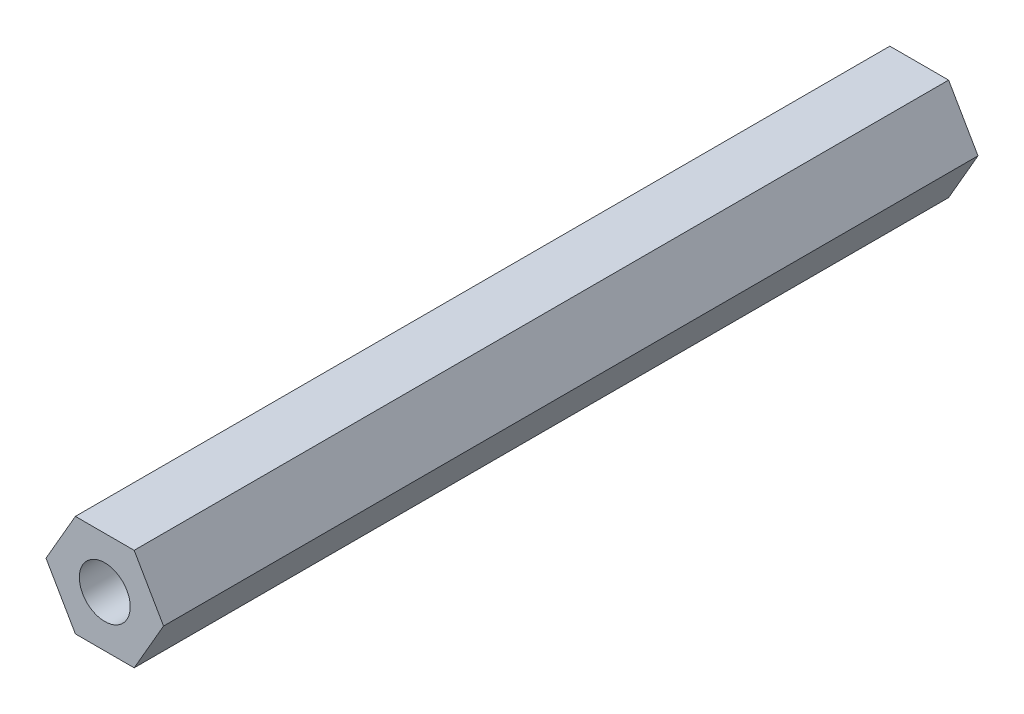
SolidWorks part; units mm, degrees
ref_plane "Front Plane" through (0, 0, 0) normal (0, 0, 1) x (1, 0, 0)
ref_plane "Top Plane" through (0, 0, 0) normal (0, 1, 0) x (1, 0, 0)
ref_plane "Right Plane" through (0, 0, 0) normal (1, 0, 0) x (0, 0, -1)
sketch "Sketch1" plane through (0, 0, 0) normal (0, 0, 1) x (1, 0, 0)
  line L0 (0, 6.35) -> (0, 0)
  line L1 (-7.3323, 0) -> (-3.6662, -6.35)
  line L2 (-3.6662, -6.35) -> (3.6662, -6.35)
  line L3 (3.6662, -6.35) -> (7.3323, 0)
  line L4 (7.3323, 0) -> (3.6662, 6.35)
  line L5 (3.6662, 6.35) -> (-3.6662, 6.35)
  line L6 (-3.6662, 6.35) -> (-7.3323, 0)
  circle A0 centre (0, 0) radius 6.35 construction
  dimension "D1" = 6.35
extrude "Boss-Extrude1" add sketch "Sketch1" along normal offset from surface (514.4834 mm away) 25.4 contours L5 L6 L1 L2 L3 L4 region at (-5.3313, 3.078, 0) offset beyond the face yes
sketch "Sketch2" plane through (0, 0, 514.4834) normal (0, 0, 1) x (1, 0, 0)
  circle A0 centre (0, 0) radius 3.175
  dimension "D1" = 6.35
extrude "Cut-Extrude1" cut sketch "Sketch2" against normal through all both and the other way through all contours A0 region at (0, 0, 514.4834)
sketch "Sketch3" plane through (0, 0, 0) normal (0, 0, -1) x (-1, 0, 0)
  line L1 (3.6662, -6.35) -> (7.3323, 0)
  line L2 (7.3323, 0) -> (3.6662, 6.35)
  line L3 (3.6662, 6.35) -> (-3.6662, 6.35)
  line L4 (-3.6662, 6.35) -> (-7.3323, 0)
  line L5 (-7.3323, 0) -> (-3.6662, -6.35)
  line L6 (-3.6662, -6.35) -> (3.6662, -6.35)
  circle A0 centre (0, 0) radius 6.35 construction
extrude "Cut-Extrude2" cut sketch "Sketch3" against normal blind 412.8834
